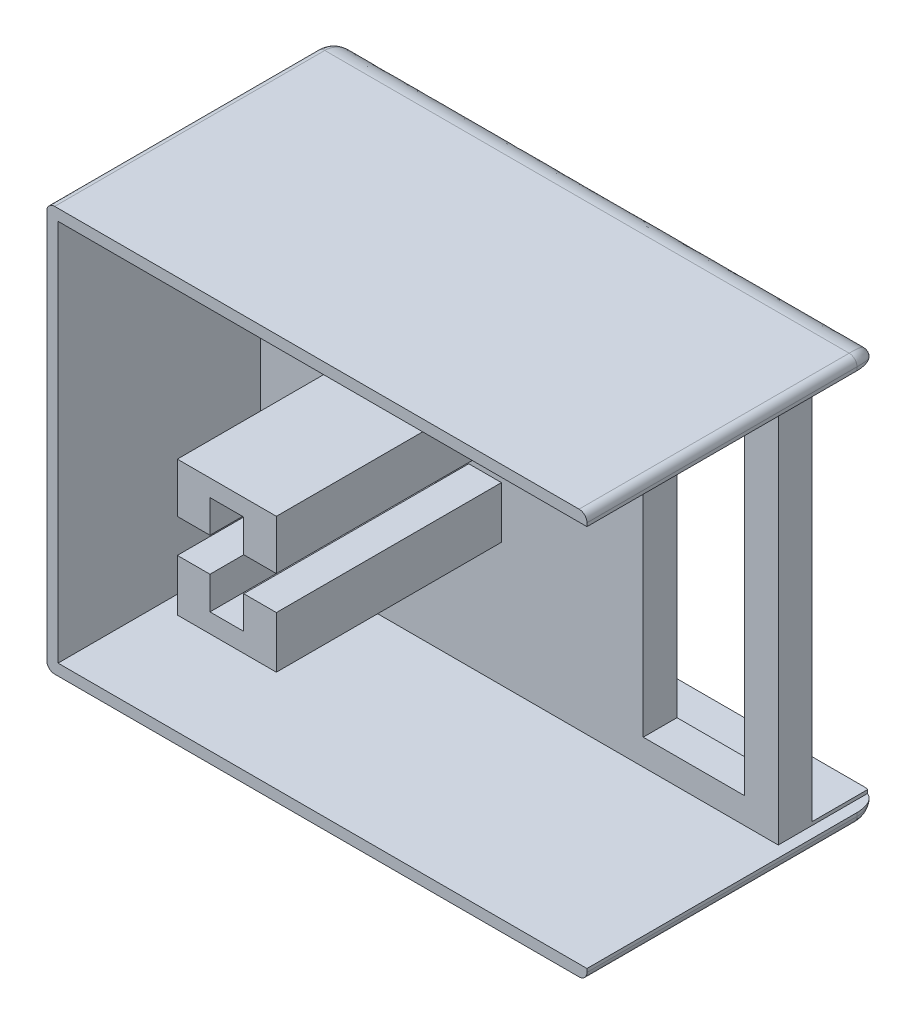
SolidWorks part; units mm, degrees
ref_plane "Front Plane" through (0, 0, 0) normal (0, 0, 1) x (1, 0, 0)
ref_plane "Top Plane" through (0, 0, 0) normal (0, 1, 0) x (1, 0, 0)
ref_plane "Right Plane" through (0, 0, 0) normal (1, 0, 0) x (0, 0, -1)
sketch "Sketch1" plane through (0, 0, 0) normal (0, 0, 1) x (1, 0, 0)
  line L1 (-12, -9) -> (12, -9)
  line L2 (-12, -9) -> (-12, 9)
  line L3 (-12, 9) -> (12, 9)
  line L4 (12, -9) -> (12, 9)
  line L5 (-12, -9) -> (12, 9) construction
  line L6 (-12, 9) -> (12, -9) construction
  point P0 (0, 0)
  dimension "D1" = 24
  dimension "D2" = 18
extrude "Boss-Extrude1" add sketch "Sketch1" along normal blind 13
fillet "Fillet1" radius 0.65 4 edges at (-12, 0, 0) (0, -9, 0) (12, 0, 0) (0, 9, 0) second distance 1 first distance on face at (0, 0, 0)
fillet "Fillet2" radius 0.35 8 edges
sketch "Sketch2" plane through (0, 0, 13) normal (0, 0, 1) x (1, 0, 0)
  line L0 (-11.65, -9) -> (11.65, -9) construction
  line L1 (11.5, 8.5) -> (-11.5, 8.5)
  line L2 (11.5, 8.5) -> (11.5, -8.5)
  line L3 (11.5, -8.5) -> (-11.5, -8.5)
  line L4 (-11.5, 8.5) -> (-11.5, -8.5)
  line L5 (12, -8.65) -> (12, 8.65) construction
  line L6 (11.65, 9) -> (-11.65, 9) construction
  line L7 (-12, 8.65) -> (-12, -8.65) construction
  dimension "D1" = 0.5
  dimension "D2" = 0.5
  dimension "D3" = 0.5
  dimension "D4" = 0.5
extrude "Cut-Extrude1" cut sketch "Sketch2" against normal blind 9
sketch "Sketch11" plane through (0, 0, 4) normal (0, 0, 1) x (1, 0, 0)
  line L1 (-5.2, -3) -> (-0.8, -3)
  line L2 (-5.2, -3) -> (-5.2, 3)
  line L3 (-5.2, 3) -> (-0.8, 3)
  line L4 (-0.8, -3) -> (-0.8, 3)
  line L5 (-5.2, -3) -> (-0.8, 3) construction
  line L6 (-5.2, 3) -> (-0.8, -3) construction
  line L7 (-11.5, 8.5) -> (-11.5, -8.5) construction
  point P0 (0, 0)
  dimension "D1" = 6
  dimension "D2" = 4.4
  dimension "D3" = 6.3
extrude "Boss-Extrude4" add sketch "Sketch11" along normal blind 10
sketch "Sketch12" plane through (0, 0, 14) normal (0, 0, 1) x (1, 0, 0)
  line L0 (-5.2, 3) -> (-5.2, -3) construction
  line L1 (-0.8, 0.7955) -> (-5.2, 0.7955)
  line L2 (-0.8, 0.7955) -> (-0.8, -0.7045)
  line L3 (-0.8, -0.7045) -> (-5.2, -0.7045)
  line L4 (-5.2, 0.7955) -> (-5.2, -0.7045)
  line L5 (-0.8, 0.7955) -> (-5.2, -0.7045) construction
  line L6 (-0.8, -0.7045) -> (-5.2, 0.7955) construction
  point P0 (-3, 0.0455)
  dimension "D1" = 1.5
extrude "Cut-Extrude6" cut sketch "Sketch12" against normal blind 10
sketch "Sketch13" plane through (0, 0, 14) normal (0, 0, 1) x (1, 0, 0)
  line L0 (-5.2, 0.7955) -> (-5.2, -0.7045) construction
  line L1 (-3.75, -2.1545) -> (-2.25, -2.1545)
  line L2 (-3.75, -2.1545) -> (-3.75, 2.2455)
  line L3 (-3.75, 2.2455) -> (-2.25, 2.2455)
  line L4 (-2.25, -2.1545) -> (-2.25, 2.2455)
  line L5 (-3.75, -2.1545) -> (-2.25, 2.2455) construction
  line L6 (-3.75, 2.2455) -> (-2.25, -2.1545) construction
  line L7 (-0.8, 0.7955) -> (-5.2, 0.7955) construction
  point P0 (-3, 0.0455)
extrude "Cut-Extrude7" cut sketch "Sketch13" against normal blind 10
sketch "Sketch14" plane through (0, 0, 13) normal (0, 0, 1) x (1, 0, 0)
  line L0 (12, -8.65) -> (12, 8.65) construction
  line L1 (11.5, 8.5) -> (12, 8.5)
  line L2 (11.5, 8.5) -> (11.5, -8.5)
  line L3 (11.5, -8.5) -> (12, -8.5)
  line L4 (12, 8.5) -> (12, -8.5)
extrude "Cut-Extrude8" cut sketch "Sketch14" against normal through all
sketch "Sketch17" plane through (0, 0, 0) normal (0, 0, -1) x (-1, 0, 0)
  line L0 (-11.35, -8.35) -> (11.35, -8.35) construction
  line L1 (-11.35, 8.35) -> (5.65, 8.35)
  line L2 (-11.35, 8.35) -> (-11.35, -8.35)
  line L3 (-11.35, -8.35) -> (5.65, -8.35)
  line L4 (5.65, 8.35) -> (5.65, -8.35)
  dimension "D1" = 17
extrude "Cut-Extrude9" cut sketch "Sketch17" against normal blind 2.5
sketch "Sketch18" plane through (11.35, 0, 0) normal (-1, 0, 0) x (0, 0, 1)
  line L0 (2.5, 8.35) -> (2.5, -8.35) construction
  line L1 (0, 8.35) -> (2.5, 8.35)
  line L2 (0, 8.35) -> (0, -8.35)
  line L3 (0, -8.35) -> (2.5, -8.35)
  line L4 (2.5, 8.35) -> (2.5, -8.35)
extrude "Cut-Extrude10" cut sketch "Sketch18" against normal through all
sketch "Sketch19" plane through (0, 0, 2.5) normal (0, 0, -1) x (-1, 0, 0)
  line L0 (5.65, 8.35) -> (-11.5, 8.35) construction
  line L1 (-10, -7.35) -> (-5.5, -7.35)
  line L2 (-10, -7.35) -> (-10, 7.35)
  line L3 (-10, 7.35) -> (-5.5, 7.35)
  line L4 (-5.5, -7.35) -> (-5.5, 7.35)
  line L5 (-10, -7.35) -> (-5.5, 7.35) construction
  line L6 (-10, 7.35) -> (-5.5, -7.35) construction
  line L7 (-11.5, -8.35) -> (5.65, -8.35) construction
  line L8 (-11.5, -8.35) -> (-11.5, 8.35) construction
  point P0 (-7.9369, 0)
  dimension "D1" = 1
  dimension "D2" = 1
  dimension "D3" = 4.5
  dimension "D4" = 1.5
extrude "Cut-Extrude11" cut sketch "Sketch19" against normal through all
